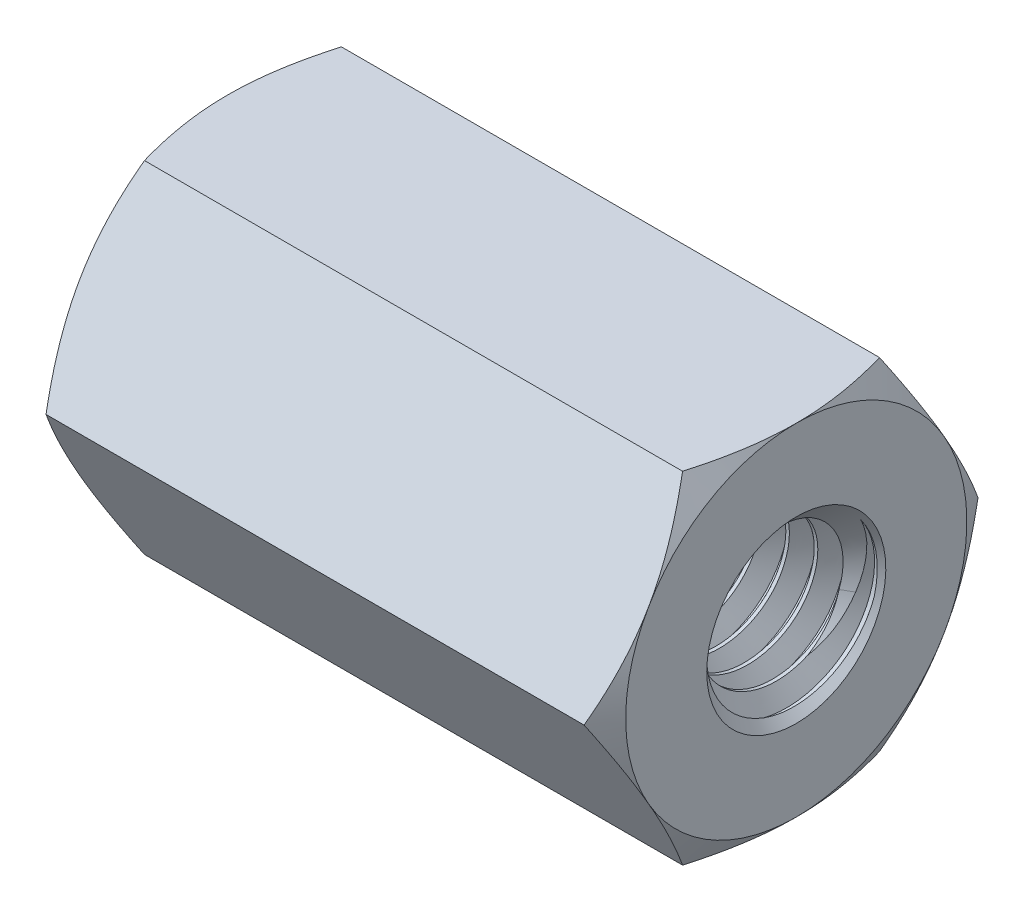
SolidWorks part; units mm, degrees
note: '?' marks a value the reader was unsure of.
material "6061-T6 (SS)"
ref_plane "Front Plane" through (0, 0, 0) normal (0, 0, 1) x (1, 0, 0)
ref_plane "Top Plane" through (0, 0, 0) normal (0, 1, 0) x (1, 0, 0)
ref_plane "Right Plane" through (0, 0, 0) normal (1, 0, 0) x (0, 0, -1)
sketch "Sketch1" plane through (0, 0, 0) normal (0, 0, 1) x (1, 0, 0)
  line L0 (0, 0) -> (10, 0) construction
  line L1 (0, 3) -> (0, -3) construction
  line L3 (0, 1.5) -> (-0.5, 1.5) construction
  line L4 (0, 3) -> (10, 3) construction
  point P6 (0, 0)
  dimension "Hex" = 6
  dimension "Pitch" = 0.5
  dimension "Thread OD" = 3
  dimension "Length" = 10
sketch "Sketch2" plane through (0, 0, 0) normal (1, 0, 0) x (0, 0, -1)
  line L0 (0, 0) -> (-1.0607, -1.0607) construction
  line L1 (1.7321, 3) -> (-1.7321, 3)
  line L2 (-1.7321, 3) -> (-3.4641, 0)
  line L3 (-3.4641, 0) -> (-1.7321, -3)
  line L4 (-1.7321, -3) -> (1.7321, -3)
  line L5 (1.7321, -3) -> (3.4641, 0)
  line L6 (3.4641, 0) -> (1.7321, 3)
  circle A0 centre (0, 0) radius 3 construction
  circle A1 centre (0, 0) radius 1.5 construction
  dimension "D1" = 45
extrude "Boss-Extrude1" add sketch "Sketch2" along normal up to vertex (10 mm away) up to point (10, 0, 0)
sketch "Sketch3" plane through (0, 0, 0) normal (0, 0, 1) x (1, 0, 0)
  line L0 (0, 1.575) -> (0.075, 1.5)
  line L1 (0, 0) -> (10, 0)
  line L2 (0, 0) -> (0, 1.575)
  line L3 (0.075, 1.5) -> (9.925, 1.5)
  line L4 (10, 0) -> (10, 1.575)
  line L9 (0, 3) -> (0, -3) construction
  line L11 (9.925, 1.5) -> (10, 1.575)
  line L12 (10, 3) -> (10, 0) construction
  line L13 (0, 0) -> (10, 0) construction
  line L14 (0, 1.5) -> (-0.5, 1.5) construction
  dimension "D1" = 3.15
  dimension "D2" = 45
revolve "Cut-Revolve1" cut sketch "Sketch3" angle 360 about L13
sketch "Sketch4" plane through (0, 0, 0) normal (-1, 0, 0) x (0, 0, 1)
  circle A0 centre (0, 0) radius 3
  circle A1 centre (0, 0) radius 3 construction
extrude "Cut-Extrude1" cut sketch "Sketch4" against normal through all draft 60 flip side to cut
sketch "Sketch5" plane through (10, 0, 0) normal (1, 0, 0) x (0, 0, -1)
  circle A0 centre (0, 0) radius 3
  circle A1 centre (0, 0) radius 3 construction
extrude "Cut-Extrude2" cut sketch "Sketch5" against normal through all draft 60 flip side to cut
ref_axis "Center Axis 1" through (0, 0, 0) along (1, 0, 0)?
sketch "Sketch6" plane through (0, 0, 0) normal (0, 0, 1) x (1, 0, 0)
  line L0 (-0.4278, 1.5) -> (-0.2139, 1.1295) construction
  line L1 (-0.2139, 1.1295) -> (0, 1.5) construction
  line L2 (0, 1.5) -> (-0.4278, 1.5) construction
  line L3 (0, 1.5) -> (-0.5, 1.5) construction
  line L5 (-0.4278, 1.5) -> (-0.4639, 1.5625) construction
  line L6 (-0.4639, 1.5625) -> (0.0361, 1.5625) construction
  line L7 (0.0361, 1.5625) -> (0, 1.5) construction
  line L8 (-0.2452, 1.1836) -> (-0.1827, 1.1836) construction
  line L9 (-0.2139, 1.5) -> (-0.2139, 1.5625) construction
  line L10 (-0.4459, 1.5312) -> (0.018, 1.5312)
  line L11 (0.018, 1.5312) -> (-0.1827, 1.1836)
  line L12 (-0.1827, 1.1836) -> (-0.2452, 1.1836)
  line L13 (-0.2452, 1.1836) -> (-0.4459, 1.5312)
  dimension "D1" = 0.0625
sketch "Sketch7" plane through (0, 0, 0) normal (-1, 0, 0) x (0, 0, 1)
  line L0 (0, 3) -> (0, -3) construction
  circle A0 centre (0, 0) radius 1.5
curve "Helix/Spiral1" pitch 0.5 height 10.5 turns 21
sweep "Sweep1" add profiles "Sketch6" path "Helix/Spiral1"
sketch "Sketch8" plane through (0, 0, 0) normal (-1, 0, 0) x (0, 0, 1)
  circle A0 centre (0, 0) radius 1.575
extrude "Cut-Extrude3" cut sketch "Sketch8" against normal through all draft 45 and the other way through all draft 45
sketch "Sketch9" plane through (10, 0, 0) normal (1, 0, 0) x (0, 0, -1)
  circle A0 centre (0, 0) radius 1.575
  circle A1 centre (0, 0) radius 1.575 construction
extrude "Cut-Extrude4" cut sketch "Sketch9" against normal through all draft 45 and the other way through all draft 45
equation "\"D1@Sketch3\"=\"Thread OD@Sketch1\"*1.05"
equation "\"D1@Sketch6\"=\"Pitch@Sketch1\"/8"
equation "\"D4@Helix/Spiral1\"=\"Pitch@Sketch1\""
equation "\"D3@Helix/Spiral1\"=\"Pitch@Sketch1\"+\"Length@Sketch1\""
equation "\"Length@Sketch1\"= \"Strut Length@Differential System Assy - Option 1.Assembly\""
